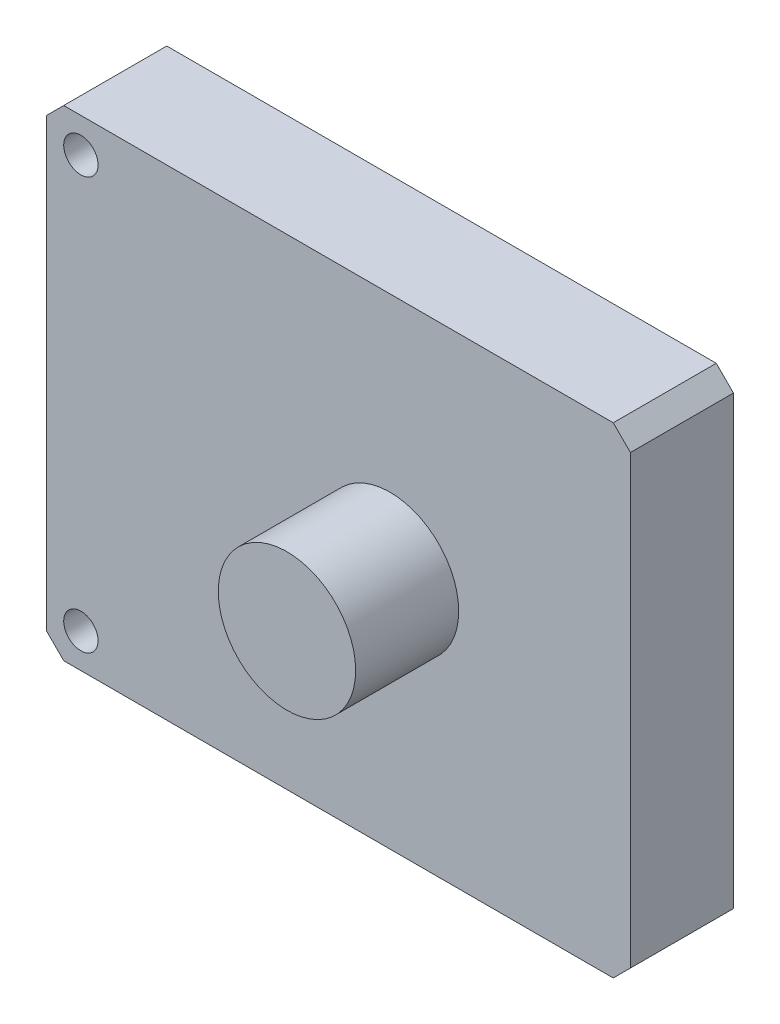
SolidWorks part; units mm, degrees
ref_plane "Alzado" through (0, 0, 0) normal (0, 0, 1) x (1, 0, 0)
ref_plane "Planta" through (0, 0, 0) normal (0, 1, 0) x (1, 0, 0)
ref_plane "Vista lateral" through (0, 0, 0) normal (1, 0, 0) x (0, 0, -1)
sketch "Croquis1" plane through (0, 0, 0) normal (0, 0, 1) x (1, 0, 0)
  line L1 (-85, 70) -> (85, 70)
  line L2 (-85, 70) -> (-85, -70)
  line L3 (-85, -70) -> (85, -70)
  line L4 (85, 70) -> (85, -70)
  line L5 (-85, 70) -> (85, -70) construction
  line L6 (-85, -70) -> (85, 70) construction
  point P0 (0, 0)
  dimension "D1" = 170
  dimension "D2" = 140
extrude "Saliente-Extruir1" add sketch "Croquis1" along normal blind 30
chamfer "Chaflán1" distance 5 angle 45 4 edges at (-85, 70, 15) (-85, -70, 15) (85, -70, 15) (85, 70, 15)
sketch "Croquis2" plane through (0, 0, 30) normal (0, 0, 1) x (1, 0, 0)
  line L0 (-75, 60) -> (-75, 0) construction
  line L1 (0, 0) -> (-116.7272, 0) construction
  line L2 (-85, 65) -> (-85, -65) construction
  circle A0 centre (-75, 60) radius 5
  circle A1 centre (15, 0) radius 20
  circle A2 centre (-75, -60) radius 5
  point P10 (15, -9.3799)
  point P11 (-49.6351, 55)
  point P14 (0, 0)
  dimension "D3" = 40
  dimension "D4" = 10
  dimension "D1" = 60
  dimension "D2" = 100
  dimension "D5" = 10
extrude "Saliente-Extruir2" add sketch "Croquis2" along normal blind 30 contours A1 region at (15, 0, 30)
extrude "Cortar-Extruir1" cut sketch "Croquis2<3>" against normal blind 30 contours A0 | A2 region at (-75, 60, 30) region at (-75, -60, 30)
sketch "Croquis2<3>" plane through (0, 0, 30) normal (0, 0, 1) x (1, 0, 0) same geometry as "Croquis2"
